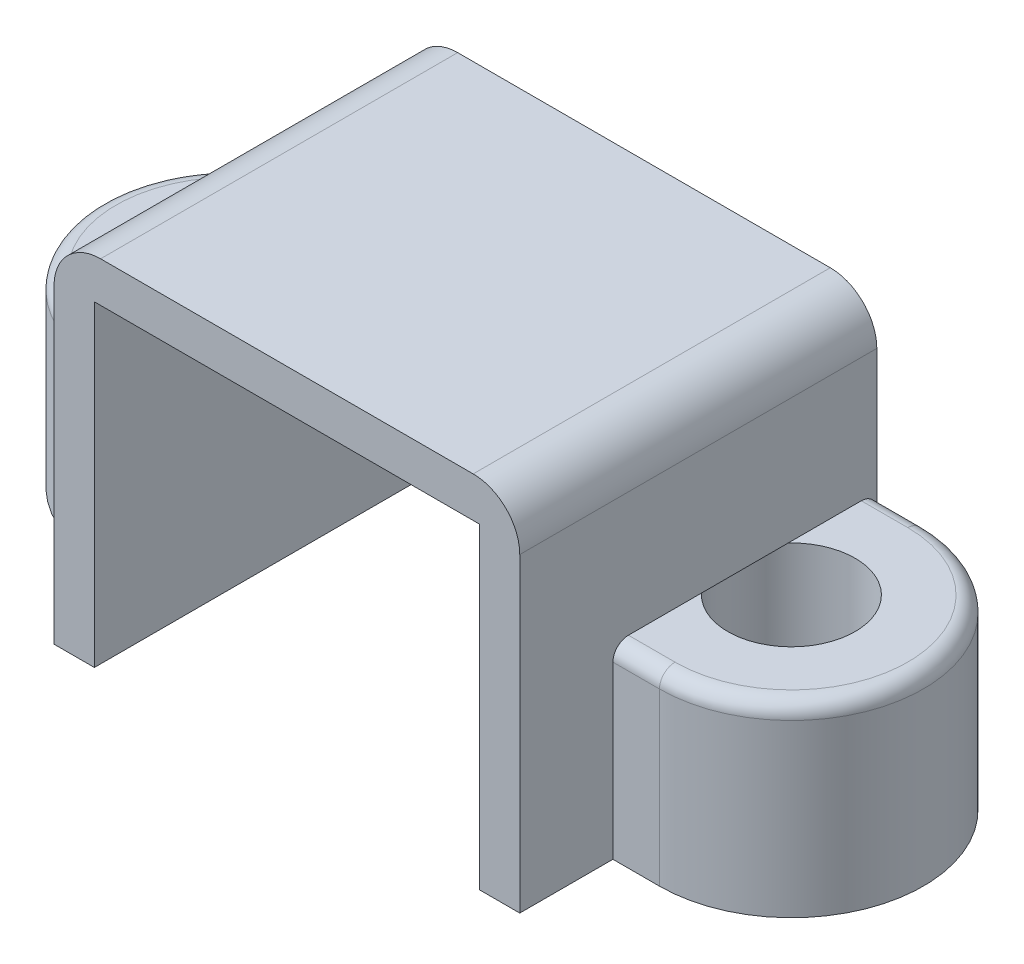
SolidWorks part; units mm, degrees
material "Custom Plastic"
ref_plane "Front Plane" through (0, 0, 0) normal (0, 0, 1) x (1, 0, 0)
ref_plane "Top Plane" through (0, 0, 0) normal (0, 1, 0) x (1, 0, 0)
ref_plane "Right Plane" through (0, 0, 0) normal (1, 0, 0) x (0, 0, -1)
sketch "Sketch1" plane through (0, 0, 0) normal (0, 0, 1) x (1, 0, 0)
  line L0 (0, -210.3757) -> (0, 10308.4069) construction
  line L1 (0, 0) -> (6, 0)
  line L2 (6, 0) -> (6, -10)
  line L3 (0, 1.5) -> (7.5, 1.5)
  line L4 (7.5, 1.5) -> (7.5, -10)
  line L5 (7.5, -10) -> (6, -10)
  line L6 (-7.5, -10) -> (-6, -10)
  line L7 (-7.5, 1.5) -> (-7.5, -10)
  line L8 (0, 1.5) -> (-7.5, 1.5)
  line L9 (-6, 0) -> (-6, -10)
  line L10 (0, 0) -> (-6, 0)
  dimension "D1" = 12
  dimension "D2" = 10
  dimension "D3" = 1.5
extrude "Boss-Extrude1" add sketch "Sketch1" along normal blind 11.5
sketch "Sketch3" plane through (0, -10, 0) normal (0, -1, 0) x (1, 0, 0)
  line L0 (0, -1000) -> (0, 49000) construction
  line L1 (7.5, 0) -> (-7.5, 0) construction
  line L2 (7.5, 0) -> (7.5, 8.5)
  line L3 (7.5, 11.5) -> (7.5, 0) construction
  line L4 (7.5, 0) -> (9, 0)
  line L5 (7.5, 8.5) -> (9, 8.5)
  line L6 (-7.5, 8.5) -> (-9, 8.5)
  line L7 (-7.5, 0) -> (-9, 0)
  line L8 (-7.5, 0) -> (-7.5, 8.5)
  arc A0 (9, 0) -> (9, 8.5) centre (9, 4.25) ccw
  arc A1 (-9, 0) -> (-9, 8.5) centre (-9, 4.25) cw
  point P5 (0, 0)
  point P10 (7.5, 4.25)
  point P11 (0, 0)
  point P16 (0, 0)
  point P22 (-7.5, 4.25)
  dimension "D1" = 8.5
  dimension "D2" = 1.5
extrude "Boss-Extrude2" add sketch "Sketch3" against normal blind 6
sketch "Sketch4" plane through (0, -10, 0) normal (0, -1, 0) x (1, 0, 0)
  line L1 (0, -1000) -> (0, 49000) construction
  circle A0 centre (-9, 4.25) radius 2.05
  arc A1 (-9, 8.5) -> (-9, 0) centre (-9, 4.25) ccw construction
  circle A2 centre (9, 4.25) radius 2.05
  dimension "D1" = 4.1
extrude "Cut-Extrude1" cut sketch "Sketch4" against normal up to surface (6 mm away) up to face at (9.3125, -4, 4.25)
fillet "Fillet1" radius 1.5 2 edges at (-7.5, 1.5, 5.75) (7.5, 1.5, 5.75)
sketch "Sketch6" plane through (0, 0, 0) normal (0, 0, -1) x (-1, 0, 0)
  line L0 (6, -10) -> (6, 0) construction
  line L1 (6, 0) -> (-6, 0) construction
  line L2 (-6, 0) -> (-6, -10) construction
  line L3 (6, -10) -> (6, 0)
  line L4 (6, 0) -> (-6, 0)
  line L5 (-6, 0) -> (-6, -10)
  line L6 (6.2, -10) -> (6.2, 0.2)
  line L7 (6.2, 0.2) -> (-6.2, 0.2)
  line L8 (-6.2, 0.2) -> (-6.2, -10)
  line L9 (6.2, -10) -> (6, -10)
  line L10 (-6, -10) -> (-6.2, -10)
extrude "Cut-Extrude2" cut sketch "Sketch6" against normal through all
fillet "Fillet2" radius 0.5 6 edges at (8.25, -4, 0) (8.25, -4, 8.5) (13.25, -4, 4.25) (-8.25, -4, 8.5) (-8.25, -4, 0) (-13.25, -4, 4.25)
equation "\"Hole_Diameter\"= 4.1mm"
equation "\"Hole_Depth\"= 6mm"
equation "\"Motor_Slot_Offset\"= 0.2mm"
equation "\"D1@Sketch6\"=\"Motor_Slot_Offset\""
equation "\"D1@Sketch4\"=\"Hole_Diameter\""
equation "\"D1@Boss-Extrude2\"=\"Hole_Depth\""
